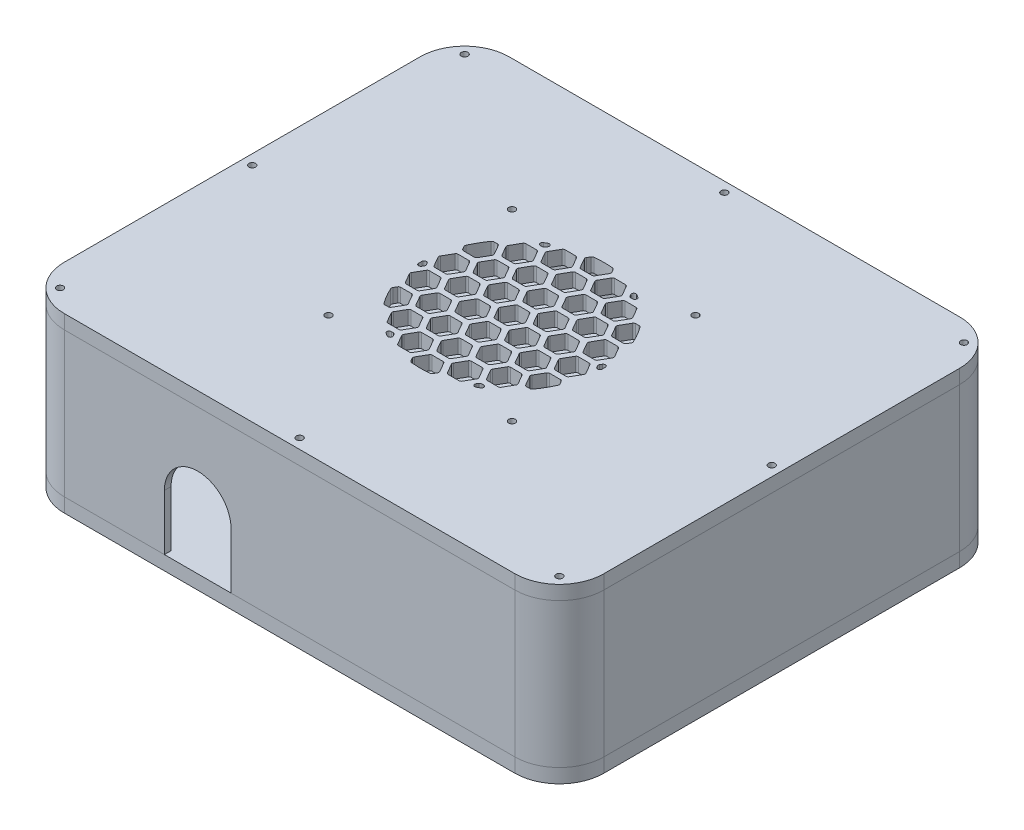
SolidWorks part; units mm, degrees
ref_plane "Front Plane" through (0, 0, 0) normal (0, 0, 1) x (1, 0, 0)
ref_plane "Top Plane" through (0, 0, 0) normal (0, 1, 0) x (1, 0, 0)
ref_plane "Right Plane" through (0, 0, 0) normal (1, 0, 0) x (0, 0, -1)
sketch "Sketch1" plane through (0, 0, 0) normal (0, 1, 0) x (1, 0, 0)
  line L0 (0, 100) -> (242.6, 100) construction
  line L1 (0, 0) -> (242.6, 0)
  line L2 (0, 0) -> (0, 200)
  line L3 (0, 200) -> (242.6, 200)
  line L4 (242.6, 0) -> (242.6, 200)
  line L6 (89, 170) -> (165.6, 170) construction
  line L7 (89, 170) -> (89, 15) construction
  line L8 (89, 15) -> (165.6, 15) construction
  line L9 (165.6, 170) -> (165.6, 15) construction
  line L10 (15, 106) -> (84, 106) construction
  line L11 (15, 106) -> (15, 15) construction
  line L12 (15, 15) -> (84, 15) construction
  line L13 (84, 106) -> (84, 15) construction
  line L14 (170.6, 127) -> (230.6, 127) construction
  line L15 (170.6, 127) -> (170.6, 15) construction
  line L16 (170.6, 15) -> (230.6, 15) construction
  line L17 (230.6, 127) -> (230.6, 15) construction
  line L22 (15, 170) -> (84, 170) construction
  line L23 (15, 170) -> (15, 121) construction
  line L24 (15, 121) -> (84, 121) construction
  line L25 (84, 170) -> (84, 121) construction
  dimension "D1" = 76.6
  dimension "D2" = 155
  dimension "D3" = 69
  dimension "D4" = 91
  dimension "D5" = 60
  dimension "D6" = 112
  dimension "D7" = 15
  dimension "D8" = 5
  dimension "D9" = 5
  dimension "D10" = 12
  dimension "D11" = 30
  dimension "D12" = 15
  dimension "D13" = 15
extrude "Boss-Extrude1" add sketch "Sketch1" along normal blind 6.35
fillet "Fillet1" radius 20 4 edges at (0, 3.175, -200) (242.6, 3.175, -200) (242.6, 3.175, 0) (0, 3.175, 0)
sketch "Sketch2" plane through (0, 6.35, 0) normal (0, 1, 0) x (1, 0, 0)
  line L0 (89, 170) -> (165.6, 170) construction
  line L1 (92.6, 167) -> (162, 167) construction
  line L2 (92.6, 167) -> (92.6, 25) construction
  line L3 (92.6, 25) -> (162, 25) construction
  line L4 (162, 167) -> (162, 25) construction
  line L5 (170.6, 127) -> (230.6, 127) construction
  line L6 (175.6, 65) -> (225.6, 65) construction
  line L7 (175.6, 65) -> (175.6, 40) construction
  line L8 (175.6, 40) -> (225.6, 40) construction
  line L9 (225.6, 65) -> (225.6, 40) construction
  line L11 (15, 170) -> (15, 121) construction
  line L12 (80.996, 125.18) -> (18.004, 125.18) construction
  line L13 (80.996, 125.18) -> (80.996, 165.82) construction
  line L14 (80.996, 165.82) -> (18.004, 165.82) construction
  line L15 (18.004, 125.18) -> (18.004, 165.82) construction
  line L16 (80.996, 125.18) -> (18.004, 165.82) construction
  line L17 (80.996, 165.82) -> (18.004, 125.18) construction
  line L18 (15, 170) -> (84, 170) construction
  line L19 (20, 0) -> (222.6, 0) construction
  circle A0 centre (92.6, 167) radius 1.5
  circle A1 centre (92.6, 25) radius 1.5
  circle A2 centre (162, 25) radius 1.5
  circle A3 centre (162, 167) radius 1.5
  circle A4 centre (175.6, 65) radius 1.5
  circle A5 centre (175.6, 40) radius 1.5
  circle A6 centre (225.6, 65) radius 1.5
  circle A7 centre (225.6, 40) radius 1.5
  circle A8 centre (18.004, 165.82) radius 1.5
  circle A9 centre (80.996, 165.82) radius 1.5
  circle A10 centre (80.996, 125.18) radius 1.5
  circle A11 centre (18.004, 125.18) radius 1.5
  point P6 (127.3, 167)
  point P7 (127.3, 170)
  point P20 (200.6, 65)
  point P23 (200.6, 127)
  point P26 (49.5, 145.5)
  point P34 (15, 145.5)
  point P37 (49.5, 170)
  dimension "D6" = 3
  dimension "D1" = 69.4
  dimension "D2" = 142
  dimension "D3" = 3
  dimension "D4" = 50
  dimension "D5" = 25
  dimension "D7" = 40
  dimension "D8" = 62.992
  dimension "D9" = 40.64
extrude "Cut-Extrude1" cut sketch "Sketch2" against normal through all
sketch "Sketch3" plane through (0, 6.35, 0) normal (0, 1, 0) x (1, 0, 0)
  line L21 (20, 20) -> (9.0398, 9.0398) construction
  line L22 (0, 180) -> (0, 20) construction
  line L23 (6.565, 11.5147) -> (5.7618, 10.7116)
  line L24 (11.5147, 6.565) -> (10.7116, 5.7618)
  line L25 (0, 100) -> (242.6, 100) construction
  line L26 (121.3, 200) -> (121.3, 0) construction
  line L27 (231.0853, 6.565) -> (231.8884, 5.7618)
  line L28 (236.035, 11.5147) -> (236.8382, 10.7116)
  line L29 (236.035, 188.4853) -> (236.8382, 189.2884)
  line L30 (231.0853, 193.435) -> (231.8884, 194.2382)
  line L31 (11.5147, 193.435) -> (10.7116, 194.2382)
  line L32 (6.565, 188.4853) -> (5.7618, 189.2884)
  line L33 (242.6, 20) -> (242.6, 180) construction
  line L34 (20, 0) -> (222.6, 0) construction
  line L35 (222.6, 200) -> (20, 200) construction
  line L36 (20, 20) -> (20, 12.5101) construction
  line L37 (3, 180) -> (3, 20)
  line L38 (20, 3) -> (222.6, 3)
  line L39 (239.6, 20) -> (239.6, 180)
  line L40 (222.6, 197) -> (20, 197)
  line L41 (222.6, 200) -> (20, 200)
  line L42 (0, 180) -> (0, 20)
  line L43 (20, 0) -> (222.6, 0)
  line L44 (242.6, 20) -> (242.6, 180)
  line L45 (222.6, 200) -> (20, 200)
  line L46 (0, 180) -> (0, 20)
  line L47 (20, 0) -> (222.6, 0)
  line L48 (242.6, 20) -> (242.6, 180)
  line L49 (4.5, 103.5) -> (3, 103.5)
  line L50 (3, 103.5) -> (3, 96.5)
  line L51 (3, 96.5) -> (4.5, 96.5)
  line L52 (239.6, 103.5) -> (239.6, 96.5)
  line L53 (238.1, 103.5) -> (239.6, 103.5)
  line L54 (239.6, 96.5) -> (238.1, 96.5)
  line L55 (117.8, 195.5) -> (117.8, 197)
  line L56 (124.8, 195.5) -> (124.8, 197)
  line L57 (117.8, 197) -> (124.8, 197)
  line L58 (117.8, 4.5) -> (117.8, 3)
  line L59 (124.8, 4.5) -> (124.8, 3)
  line L60 (117.8, 3) -> (124.8, 3)
  arc A22 (10.7116, 194.2382) -> (5.7618, 189.2884) centre (20, 180) ccw
  arc A24 (5.7618, 10.7116) -> (10.7116, 5.7618) centre (20, 20) ccw
  arc A26 (231.8884, 5.7618) -> (236.8382, 10.7116) centre (222.6, 20) ccw
  arc A28 (236.8382, 189.2884) -> (231.8884, 194.2382) centre (222.6, 180) ccw
  arc A43 (11.5147, 6.565) -> (6.565, 11.5147) centre (9.0398, 9.0398) ccw
  circle A44 centre (9.0398, 9.0398) radius 1.5
  circle A45 centre (233.5602, 9.0398) radius 1.5
  arc A46 (231.0853, 6.565) -> (236.035, 11.5147) centre (233.5602, 9.0398) cw
  circle A47 centre (233.5602, 190.9602) radius 1.5
  arc A48 (231.0853, 193.435) -> (236.035, 188.4853) centre (233.5602, 190.9602) ccw
  circle A49 centre (9.0398, 190.9602) radius 1.5
  arc A50 (11.5147, 193.435) -> (6.565, 188.4853) centre (9.0398, 190.9602) cw
  arc A51 (222.6, 0) -> (242.6, 20) centre (222.6, 20) ccw construction
  arc A52 (0, 20) -> (20, 0) centre (20, 20) ccw construction
  arc A53 (242.6, 180) -> (222.6, 200) centre (222.6, 180) ccw construction
  arc A54 (20, 200) -> (0, 180) centre (20, 180) ccw construction
  arc A55 (3, 20) -> (20, 3) centre (20, 20) ccw
  arc A56 (222.6, 3) -> (239.6, 20) centre (222.6, 20) ccw
  arc A57 (239.6, 180) -> (222.6, 197) centre (222.6, 180) ccw
  arc A58 (20, 197) -> (3, 180) centre (20, 180) ccw
  arc A59 (20, 200) -> (0, 180) centre (20, 180) ccw
  arc A60 (0, 20) -> (20, 0) centre (20, 20) ccw
  arc A61 (222.6, 0) -> (242.6, 20) centre (222.6, 20) ccw
  arc A62 (242.6, 180) -> (222.6, 200) centre (222.6, 180) ccw
  arc A63 (20, 200) -> (0, 180) centre (20, 180) ccw
  arc A64 (0, 20) -> (20, 0) centre (20, 20) ccw
  arc A65 (222.6, 0) -> (242.6, 20) centre (222.6, 20) ccw
  arc A66 (242.6, 180) -> (222.6, 200) centre (222.6, 180) ccw
  arc A67 (4.5, 96.5) -> (4.5, 103.5) centre (4.5, 100) ccw
  circle A68 centre (4.5, 100) radius 1.5
  arc A69 (238.1, 96.5) -> (238.1, 103.5) centre (238.1, 100) cw
  circle A70 centre (238.1, 100) radius 1.5
  circle A71 centre (121.3, 195.5) radius 1.5
  arc A72 (117.8, 195.5) -> (124.8, 195.5) centre (121.3, 195.5) ccw
  circle A73 centre (121.3, 4.5) radius 1.5
  arc A74 (117.8, 4.5) -> (124.8, 4.5) centre (121.3, 4.5) cw
  line M50 (222.6, 200) -> (20, 200)
  arc M51 (20, 200) -> (0, 180) centre (20, 180) ccw
  line M52 (0, 180) -> (0, 20)
  arc M53 (0, 20) -> (20, 0) centre (20, 20) ccw
  line M54 (20, 0) -> (222.6, 0)
  arc M55 (222.6, 0) -> (242.6, 20) centre (222.6, 20) ccw
  line M56 (242.6, 20) -> (242.6, 180)
  arc M57 (242.6, 180) -> (222.6, 200) centre (222.6, 180) ccw
  dimension "D3" = 0
  dimension "D4" = 7
  dimension "D5" = 3
  dimension "D1" = 3
  dimension "D7" = 3
  dimension "D6" = 3
  dimension "D2" = 45
extrude "Boss-Extrude2" add sketch "Sketch3" along normal blind 65 separate body contours M57 M50 M51 M52 M53 M54 M55 M56 | A50 L31 A22 A49 L32 | L37 A68 L50 L51 A67 L49 | A24 A44 L24 A43 L23 | A46 L27 A26 A45 L28 | A74 L58 L38 A73 L60 L59 | L39 A70 L52 L53 A69 L54 | L30 A48 L29 A28 A47 | L55 A72 L56 L40 A71 L57 region at (11.4469, 6.35, -11.4469) region at (3.086, 6.35, -98.25) region at (117.886, 6.35, -3.75) region at (6.8741, 6.35, -190.6517) region at (231.5546, 6.35, -6.2312) region at (119.55, 6.35, -196.914) region at (238.85, 6.35, -96.586) region at (233.2517, 6.35, -193.1259) region at (236.5198, 6.35, -193.9198)
fillet "Fillet5" radius 2 16 edges at (10.7116, 38.85, -194.2382) (5.7618, 38.85, -189.2884) (3, 38.85, -103.5) (3, 38.85, -96.5) (5.7618, 38.85, -10.7116) (10.7116, 38.85, -5.7618) (117.8, 38.85, -3) (124.8, 38.85, -3) (231.8884, 38.85, -5.7618) (236.8382, 38.85, -10.7116) (239.6, 38.85, -96.5) (239.6, 38.85, -103.5) (231.8884, 38.85, -194.2382) (124.8, 38.85, -197) (117.8, 38.85, -197) (236.8382, 38.85, -189.2884)
sketch "Sketch4" plane through (0, 71.35, 0) normal (0, 1, 0) x (1, 0, 0)
  line L4 (0, 180) -> (0, 20)
  line L5 (222.6, 200) -> (20, 200)
  line L6 (242.6, 20) -> (242.6, 180)
  line L7 (20, 0) -> (222.6, 0)
  line L8 (0, 180) -> (0, 20)
  line L9 (222.6, 200) -> (20, 200)
  line L10 (242.6, 20) -> (242.6, 180)
  line L11 (20, 0) -> (222.6, 0)
  arc A4 (20, 200) -> (0, 180) centre (20, 180) ccw
  arc A5 (242.6, 180) -> (222.6, 200) centre (222.6, 180) ccw
  arc A6 (222.6, 0) -> (242.6, 20) centre (222.6, 20) ccw
  arc A7 (0, 20) -> (20, 0) centre (20, 20) ccw
  arc A8 (20, 200) -> (0, 180) centre (20, 180) ccw
  arc A9 (242.6, 180) -> (222.6, 200) centre (222.6, 180) ccw
  arc A10 (222.6, 0) -> (242.6, 20) centre (222.6, 20) ccw
  arc A11 (0, 20) -> (20, 0) centre (20, 20) ccw
  dimension "D1" = 0
extrude "Boss-Extrude4" add sketch "Sketch4" along normal blind 6.35 separate body
sketch "Sketch5" plane through (0, 77.7, 0) normal (0, 1, 0) x (1, 0, 0)
  line L1 (80.05, 141.25) -> (162.55, 141.25) construction
  line L2 (80.05, 141.25) -> (80.05, 58.75) construction
  line L3 (80.05, 58.75) -> (162.55, 58.75) construction
  line L4 (162.55, 141.25) -> (162.55, 58.75) construction
  line L5 (80.05, 141.25) -> (162.55, 58.75) construction
  line L6 (80.05, 58.75) -> (162.55, 141.25) construction
  line L8 (222.6, 200) -> (20, 200) construction
  line L9 (0, 180) -> (0, 20) construction
  circle A0 centre (80.05, 141.25) radius 1.5
  circle A1 centre (80.05, 58.75) radius 1.5
  circle A2 centre (162.55, 58.75) radius 1.5
  circle A3 centre (162.55, 141.25) radius 1.5
  point P0 (121.3, 100)
  point P11 (121.3, 200)
  point P12 (0, 100)
  dimension "D2" = 3
  dimension "D1" = 82.5
extrude "Cut-Extrude2" cut sketch "Sketch5" against normal through all
sketch "Sketch6" plane through (0, 77.7, 0) normal (0, 1, 0) x (1, 0, 0)
  circle A20 centre (121.3, 4.5) radius 1.5 construction
  circle A21 centre (233.5602, 9.0398) radius 1.5 construction
  circle A22 centre (238.1, 100) radius 1.5 construction
  circle A23 centre (233.5602, 190.9602) radius 1.5 construction
  circle A24 centre (121.3, 195.5) radius 1.5 construction
  circle A25 centre (9.0398, 190.9602) radius 1.5 construction
  circle A26 centre (4.5, 100) radius 1.5 construction
  circle A27 centre (9.0398, 9.0398) radius 1.5 construction
  circle A28 centre (121.3, 4.5) radius 1.5
  circle A29 centre (233.5602, 9.0398) radius 1.5
  circle A30 centre (238.1, 100) radius 1.5
  circle A31 centre (233.5602, 190.9602) radius 1.5
  circle A32 centre (121.3, 195.5) radius 1.5
  circle A33 centre (9.0398, 190.9602) radius 1.5
  circle A34 centre (4.5, 100) radius 1.5
  circle A35 centre (9.0398, 9.0398) radius 1.5
extrude "Cut-Extrude3" cut sketch "Sketch6" against normal through all
sketch "Sketch7" plane through (0, 77.7, 0) normal (0, 1, 0) x (1, 0, 0)
  line L0 (80.05, 141.25) -> (162.55, 141.25) construction
  line L1 (80.05, 141.25) -> (80.05, 58.75) construction
  line L2 (80.05, 58.75) -> (162.55, 58.75) construction
  line L3 (162.55, 141.25) -> (162.55, 58.75) construction
  line L4 (80.05, 141.25) -> (162.55, 141.25) construction
  line L5 (80.05, 141.25) -> (80.05, 58.75) construction
  line L6 (80.05, 58.75) -> (162.55, 58.75) construction
  line L7 (162.55, 141.25) -> (162.55, 58.75) construction
  line L8 (157.7952, 124.5346) -> (151.7952, 124.5346)
  line L9 (124.3, 105.1962) -> (118.3, 105.1962)
  line L10 (118.3, 105.1962) -> (115.3, 100)
  line L11 (115.3, 100) -> (118.3, 94.8038)
  line L12 (118.3, 94.8038) -> (124.3, 94.8038)
  line L13 (124.3, 94.8038) -> (127.3, 100)
  line L14 (127.3, 100) -> (124.3, 105.1962)
  line L15 (138.4651, 106.4462) -> (135.4651, 111.6423)
  line L16 (135.4651, 111.6423) -> (129.4651, 111.6423)
  line L17 (129.4651, 111.6423) -> (126.4651, 106.4462)
  line L18 (126.4651, 106.4462) -> (129.4651, 101.25)
  line L19 (129.4651, 101.25) -> (135.4651, 101.25)
  line L20 (135.4651, 101.25) -> (138.4651, 106.4462)
  line L21 (127.3, 112.8923) -> (124.3, 118.0885)
  line L22 (124.3, 118.0885) -> (118.3, 118.0885)
  line L23 (118.3, 118.0885) -> (115.3, 112.8923)
  line L24 (115.3, 112.8923) -> (118.3, 107.6962)
  line L25 (118.3, 107.6962) -> (124.3, 107.6962)
  line L26 (124.3, 107.6962) -> (127.3, 112.8923)
  line L27 (135.4651, 124.5346) -> (129.4651, 124.5346)
  line L28 (129.4651, 124.5346) -> (126.4651, 119.3385)
  line L29 (126.4651, 119.3385) -> (129.4651, 114.1423)
  line L30 (129.4651, 114.1423) -> (135.4651, 114.1423)
  line L31 (135.4651, 114.1423) -> (138.4651, 119.3385)
  line L32 (138.4651, 119.3385) -> (135.4651, 124.5346)
  line L33 (151.7952, 124.5346) -> (148.7952, 119.3385)
  line L34 (148.7952, 119.3385) -> (151.7952, 114.1423)
  line L35 (151.7952, 114.1423) -> (157.7952, 114.1423)
  line L36 (157.7952, 114.1423) -> (160.7952, 119.3385)
  line L37 (160.7952, 119.3385) -> (157.7952, 124.5346)
  line L38 (149.6301, 112.8923) -> (146.6301, 118.0885)
  line L39 (146.6301, 118.0885) -> (140.6301, 118.0885)
  line L40 (140.6301, 118.0885) -> (137.6301, 112.8923)
  line L41 (137.6301, 112.8923) -> (140.6301, 107.6962)
  line L42 (140.6301, 107.6962) -> (146.6301, 107.6962)
  line L43 (146.6301, 107.6962) -> (149.6301, 112.8923)
  line L44 (146.6301, 105.1962) -> (140.6301, 105.1962)
  line L45 (140.6301, 105.1962) -> (137.6301, 100)
  line L46 (137.6301, 100) -> (140.6301, 94.8038)
  line L47 (140.6301, 94.8038) -> (146.6301, 94.8038)
  line L48 (146.6301, 94.8038) -> (149.6301, 100)
  line L49 (149.6301, 100) -> (146.6301, 105.1962)
  line L50 (160.7952, 106.4462) -> (157.7952, 111.6423)
  line L51 (157.7952, 111.6423) -> (151.7952, 111.6423)
  line L52 (151.7952, 111.6423) -> (148.7952, 106.4462)
  line L53 (148.7952, 106.4462) -> (151.7952, 101.25)
  line L54 (151.7952, 101.25) -> (157.7952, 101.25)
  line L55 (157.7952, 101.25) -> (160.7952, 106.4462)
  line L56 (180.1253, 124.5346) -> (174.1253, 124.5346)
  line L57 (174.1253, 124.5346) -> (171.1253, 119.3385)
  line L58 (171.1253, 119.3385) -> (174.1253, 114.1423)
  line L59 (174.1253, 114.1423) -> (180.1253, 114.1423)
  line L60 (180.1253, 114.1423) -> (183.1253, 119.3385)
  line L61 (183.1253, 119.3385) -> (180.1253, 124.5346)
  line L62 (171.9603, 112.8923) -> (168.9603, 118.0885)
  line L63 (168.9603, 118.0885) -> (162.9603, 118.0885)
  line L64 (162.9603, 118.0885) -> (159.9603, 112.8923)
  line L65 (159.9603, 112.8923) -> (162.9603, 107.6962)
  line L66 (162.9603, 107.6962) -> (168.9603, 107.6962)
  line L67 (168.9603, 107.6962) -> (171.9603, 112.8923)
  line L68 (168.9603, 105.1962) -> (162.9603, 105.1962)
  line L69 (162.9603, 105.1962) -> (159.9603, 100)
  line L70 (159.9603, 100) -> (162.9603, 94.8038)
  line L71 (162.9603, 94.8038) -> (168.9603, 94.8038)
  line L72 (168.9603, 94.8038) -> (171.9603, 100)
  line L73 (171.9603, 100) -> (168.9603, 105.1962)
  line L74 (183.1253, 106.4462) -> (180.1253, 111.6423)
  line L75 (180.1253, 111.6423) -> (174.1253, 111.6423)
  line L76 (174.1253, 111.6423) -> (171.1253, 106.4462)
  line L77 (171.1253, 106.4462) -> (174.1253, 101.25)
  line L78 (174.1253, 101.25) -> (180.1253, 101.25)
  line L79 (180.1253, 101.25) -> (183.1253, 106.4462)
  line L80 (157.7952, 150.3192) -> (151.7952, 150.3192)
  line L81 (151.7952, 150.3192) -> (148.7952, 145.1231)
  line L82 (148.7952, 145.1231) -> (151.7952, 139.9269)
  line L83 (151.7952, 139.9269) -> (157.7952, 139.9269)
  line L84 (157.7952, 139.9269) -> (160.7952, 145.1231)
  line L85 (160.7952, 145.1231) -> (157.7952, 150.3192)
  line L86 (149.6301, 138.6769) -> (146.6301, 143.8731)
  line L87 (146.6301, 143.8731) -> (140.6301, 143.8731)
  line L88 (140.6301, 143.8731) -> (137.6301, 138.6769)
  line L89 (137.6301, 138.6769) -> (140.6301, 133.4808)
  line L90 (140.6301, 133.4808) -> (146.6301, 133.4808)
  line L91 (146.6301, 133.4808) -> (149.6301, 138.6769)
  line L92 (146.6301, 130.9808) -> (140.6301, 130.9808)
  line L93 (140.6301, 130.9808) -> (137.6301, 125.7846)
  line L94 (137.6301, 125.7846) -> (140.6301, 120.5885)
  line L95 (140.6301, 120.5885) -> (146.6301, 120.5885)
  line L96 (146.6301, 120.5885) -> (149.6301, 125.7846)
  line L97 (149.6301, 125.7846) -> (146.6301, 130.9808)
  line L98 (160.7952, 132.2308) -> (157.7952, 137.4269)
  line L99 (157.7952, 137.4269) -> (151.7952, 137.4269)
  line L100 (151.7952, 137.4269) -> (148.7952, 132.2308)
  line L101 (148.7952, 132.2308) -> (151.7952, 127.0346)
  line L102 (151.7952, 127.0346) -> (157.7952, 127.0346)
  line L103 (157.7952, 127.0346) -> (160.7952, 132.2308)
  line L104 (180.1253, 150.3192) -> (174.1253, 150.3192)
  line L105 (174.1253, 150.3192) -> (171.1253, 145.1231)
  line L106 (171.1253, 145.1231) -> (174.1253, 139.9269)
  line L107 (174.1253, 139.9269) -> (180.1253, 139.9269)
  line L108 (180.1253, 139.9269) -> (183.1253, 145.1231)
  line L109 (183.1253, 145.1231) -> (180.1253, 150.3192)
  line L110 (171.9603, 138.6769) -> (168.9603, 143.8731)
  line L111 (168.9603, 143.8731) -> (162.9603, 143.8731)
  line L112 (162.9603, 143.8731) -> (159.9603, 138.6769)
  line L113 (159.9603, 138.6769) -> (162.9603, 133.4808)
  line L114 (162.9603, 133.4808) -> (168.9603, 133.4808)
  line L115 (168.9603, 133.4808) -> (171.9603, 138.6769)
  line L116 (168.9603, 130.9808) -> (162.9603, 130.9808)
  line L117 (162.9603, 130.9808) -> (159.9603, 125.7846)
  line L118 (159.9603, 125.7846) -> (162.9603, 120.5885)
  line L119 (162.9603, 120.5885) -> (168.9603, 120.5885)
  line L120 (168.9603, 120.5885) -> (171.9603, 125.7846)
  line L121 (171.9603, 125.7846) -> (168.9603, 130.9808)
  line L122 (183.1253, 132.2308) -> (180.1253, 137.4269)
  line L123 (180.1253, 137.4269) -> (174.1253, 137.4269)
  line L124 (174.1253, 137.4269) -> (171.1253, 132.2308)
  line L125 (171.1253, 132.2308) -> (174.1253, 127.0346)
  line L126 (174.1253, 127.0346) -> (180.1253, 127.0346)
  line L127 (180.1253, 127.0346) -> (183.1253, 132.2308)
  line L128 (135.4651, 150.3192) -> (129.4651, 150.3192)
  line L129 (129.4651, 150.3192) -> (126.4651, 145.1231)
  line L130 (126.4651, 145.1231) -> (129.4651, 139.9269)
  line L131 (129.4651, 139.9269) -> (135.4651, 139.9269)
  line L132 (135.4651, 139.9269) -> (138.4651, 145.1231)
  line L133 (138.4651, 145.1231) -> (135.4651, 150.3192)
  line L134 (127.3, 138.6769) -> (124.3, 143.8731)
  line L135 (124.3, 143.8731) -> (118.3, 143.8731)
  line L136 (118.3, 143.8731) -> (115.3, 138.6769)
  line L137 (115.3, 138.6769) -> (118.3, 133.4808)
  line L138 (118.3, 133.4808) -> (124.3, 133.4808)
  line L139 (124.3, 133.4808) -> (127.3, 138.6769)
  line L140 (124.3, 130.9808) -> (118.3, 130.9808)
  line L141 (118.3, 130.9808) -> (115.3, 125.7846)
  line L142 (115.3, 125.7846) -> (118.3, 120.5885)
  line L143 (118.3, 120.5885) -> (124.3, 120.5885)
  line L144 (124.3, 120.5885) -> (127.3, 125.7846)
  line L145 (127.3, 125.7846) -> (124.3, 130.9808)
  line L146 (138.4651, 132.2308) -> (135.4651, 137.4269)
  line L147 (135.4651, 137.4269) -> (129.4651, 137.4269)
  line L148 (129.4651, 137.4269) -> (126.4651, 132.2308)
  line L149 (126.4651, 132.2308) -> (129.4651, 127.0346)
  line L150 (129.4651, 127.0346) -> (135.4651, 127.0346)
  line L151 (135.4651, 127.0346) -> (138.4651, 132.2308)
  line L152 (124.3, 92.3038) -> (118.3, 92.3038)
  line L153 (118.3, 92.3038) -> (115.3, 87.1077)
  line L154 (115.3, 87.1077) -> (118.3, 81.9115)
  line L155 (118.3, 81.9115) -> (124.3, 81.9115)
  line L156 (124.3, 81.9115) -> (127.3, 87.1077)
  line L157 (127.3, 87.1077) -> (124.3, 92.3038)
  line L158 (138.4651, 93.5538) -> (135.4651, 98.75)
  line L159 (135.4651, 98.75) -> (129.4651, 98.75)
  line L160 (129.4651, 98.75) -> (126.4651, 93.5538)
  line L161 (126.4651, 93.5538) -> (129.4651, 88.3577)
  line L162 (129.4651, 88.3577) -> (135.4651, 88.3577)
  line L163 (135.4651, 88.3577) -> (138.4651, 93.5538)
  line L164 (160.7952, 93.5538) -> (157.7952, 98.75)
  line L165 (157.7952, 98.75) -> (151.7952, 98.75)
  line L166 (151.7952, 98.75) -> (148.7952, 93.5538)
  line L167 (148.7952, 93.5538) -> (151.7952, 88.3577)
  line L168 (151.7952, 88.3577) -> (157.7952, 88.3577)
  line L169 (157.7952, 88.3577) -> (160.7952, 93.5538)
  line L170 (168.9603, 92.3038) -> (162.9603, 92.3038)
  line L171 (162.9603, 92.3038) -> (159.9603, 87.1077)
  line L172 (159.9603, 87.1077) -> (162.9603, 81.9115)
  line L173 (162.9603, 81.9115) -> (168.9603, 81.9115)
  line L174 (168.9603, 81.9115) -> (171.9603, 87.1077)
  line L175 (171.9603, 87.1077) -> (168.9603, 92.3038)
  line L176 (146.6301, 92.3038) -> (140.6301, 92.3038)
  line L177 (140.6301, 92.3038) -> (137.6301, 87.1077)
  line L178 (137.6301, 87.1077) -> (140.6301, 81.9115)
  line L179 (140.6301, 81.9115) -> (146.6301, 81.9115)
  line L180 (146.6301, 81.9115) -> (149.6301, 87.1077)
  line L181 (149.6301, 87.1077) -> (146.6301, 92.3038)
  line L182 (124.3, 79.4115) -> (118.3, 79.4115)
  line L183 (118.3, 79.4115) -> (115.3, 74.2154)
  line L184 (115.3, 74.2154) -> (118.3, 69.0192)
  line L185 (118.3, 69.0192) -> (124.3, 69.0192)
  line L186 (124.3, 69.0192) -> (127.3, 74.2154)
  line L187 (127.3, 74.2154) -> (124.3, 79.4115)
  line L188 (138.4651, 80.6615) -> (135.4651, 85.8577)
  line L189 (135.4651, 85.8577) -> (129.4651, 85.8577)
  line L190 (129.4651, 85.8577) -> (126.4651, 80.6615)
  line L191 (126.4651, 80.6615) -> (129.4651, 75.4654)
  line L192 (129.4651, 75.4654) -> (135.4651, 75.4654)
  line L193 (135.4651, 75.4654) -> (138.4651, 80.6615)
  line L194 (160.7952, 80.6615) -> (157.7952, 85.8577)
  line L195 (157.7952, 85.8577) -> (151.7952, 85.8577)
  line L196 (151.7952, 85.8577) -> (148.7952, 80.6615)
  line L197 (148.7952, 80.6615) -> (151.7952, 75.4654)
  line L198 (151.7952, 75.4654) -> (157.7952, 75.4654)
  line L199 (157.7952, 75.4654) -> (160.7952, 80.6615)
  line L200 (168.9603, 79.4115) -> (162.9603, 79.4115)
  line L201 (162.9603, 79.4115) -> (159.9603, 74.2154)
  line L202 (159.9603, 74.2154) -> (162.9603, 69.0192)
  line L203 (162.9603, 69.0192) -> (168.9603, 69.0192)
  line L204 (168.9603, 69.0192) -> (171.9603, 74.2154)
  line L205 (171.9603, 74.2154) -> (168.9603, 79.4115)
  line L206 (146.6301, 79.4115) -> (140.6301, 79.4115)
  line L207 (140.6301, 79.4115) -> (137.6301, 74.2154)
  line L208 (137.6301, 74.2154) -> (140.6301, 69.0192)
  line L209 (140.6301, 69.0192) -> (146.6301, 69.0192)
  line L210 (146.6301, 69.0192) -> (149.6301, 74.2154)
  line L211 (149.6301, 74.2154) -> (146.6301, 79.4115)
  line L212 (124.3, 66.5192) -> (118.3, 66.5192)
  line L213 (118.3, 66.5192) -> (115.3, 61.3231)
  line L214 (115.3, 61.3231) -> (118.3, 56.1269)
  line L215 (118.3, 56.1269) -> (124.3, 56.1269)
  line L216 (124.3, 56.1269) -> (127.3, 61.3231)
  line L217 (127.3, 61.3231) -> (124.3, 66.5192)
  line L218 (138.4651, 67.7692) -> (135.4651, 72.9654)
  line L219 (135.4651, 72.9654) -> (129.4651, 72.9654)
  line L220 (129.4651, 72.9654) -> (126.4651, 67.7692)
  line L221 (126.4651, 67.7692) -> (129.4651, 62.5731)
  line L222 (129.4651, 62.5731) -> (135.4651, 62.5731)
  line L223 (135.4651, 62.5731) -> (138.4651, 67.7692)
  line L224 (160.7952, 67.7692) -> (157.7952, 72.9654)
  line L225 (157.7952, 72.9654) -> (151.7952, 72.9654)
  line L226 (151.7952, 72.9654) -> (148.7952, 67.7692)
  line L227 (148.7952, 67.7692) -> (151.7952, 62.5731)
  line L228 (151.7952, 62.5731) -> (157.7952, 62.5731)
  line L229 (157.7952, 62.5731) -> (160.7952, 67.7692)
  line L230 (168.9603, 66.5192) -> (162.9603, 66.5192)
  line L231 (162.9603, 66.5192) -> (159.9603, 61.3231)
  line L232 (159.9603, 61.3231) -> (162.9603, 56.1269)
  line L233 (162.9603, 56.1269) -> (168.9603, 56.1269)
  line L234 (168.9603, 56.1269) -> (171.9603, 61.3231)
  line L235 (171.9603, 61.3231) -> (168.9603, 66.5192)
  line L236 (146.6301, 66.5192) -> (140.6301, 66.5192)
  line L237 (140.6301, 66.5192) -> (137.6301, 61.3231)
  line L238 (137.6301, 61.3231) -> (140.6301, 56.1269)
  line L239 (140.6301, 56.1269) -> (146.6301, 56.1269)
  line L240 (146.6301, 56.1269) -> (149.6301, 61.3231)
  line L241 (149.6301, 61.3231) -> (146.6301, 66.5192)
  line L242 (124.3, 53.6269) -> (118.3, 53.6269)
  line L243 (118.3, 53.6269) -> (115.3, 48.4308)
  line L244 (115.3, 48.4308) -> (118.3, 43.2346)
  line L245 (118.3, 43.2346) -> (124.3, 43.2346)
  line L246 (124.3, 43.2346) -> (127.3, 48.4308)
  line L247 (127.3, 48.4308) -> (124.3, 53.6269)
  line L248 (138.4651, 54.8769) -> (135.4651, 60.0731)
  line L249 (135.4651, 60.0731) -> (129.4651, 60.0731)
  line L250 (129.4651, 60.0731) -> (126.4651, 54.8769)
  line L251 (126.4651, 54.8769) -> (129.4651, 49.6808)
  line L252 (129.4651, 49.6808) -> (135.4651, 49.6808)
  line L253 (135.4651, 49.6808) -> (138.4651, 54.8769)
  line L254 (160.7952, 54.8769) -> (157.7952, 60.0731)
  line L255 (157.7952, 60.0731) -> (151.7952, 60.0731)
  line L256 (151.7952, 60.0731) -> (148.7952, 54.8769)
  line L257 (148.7952, 54.8769) -> (151.7952, 49.6808)
  line L258 (151.7952, 49.6808) -> (157.7952, 49.6808)
  line L259 (157.7952, 49.6808) -> (160.7952, 54.8769)
  line L260 (168.9603, 53.6269) -> (162.9603, 53.6269)
  line L261 (162.9603, 53.6269) -> (159.9603, 48.4308)
  line L262 (159.9603, 48.4308) -> (162.9603, 43.2346)
  line L263 (162.9603, 43.2346) -> (168.9603, 43.2346)
  line L264 (168.9603, 43.2346) -> (171.9603, 48.4308)
  line L265 (171.9603, 48.4308) -> (168.9603, 53.6269)
  line L266 (146.6301, 53.6269) -> (140.6301, 53.6269)
  line L267 (140.6301, 53.6269) -> (137.6301, 48.4308)
  line L268 (137.6301, 48.4308) -> (140.6301, 43.2346)
  line L269 (140.6301, 43.2346) -> (146.6301, 43.2346)
  line L270 (146.6301, 43.2346) -> (149.6301, 48.4308)
  line L271 (149.6301, 48.4308) -> (146.6301, 53.6269)
  line L272 (104.9699, 138.6769) -> (101.9699, 143.8731)
  line L273 (101.9699, 143.8731) -> (95.9699, 143.8731)
  line L274 (95.9699, 143.8731) -> (92.9699, 138.6769)
  line L275 (92.9699, 138.6769) -> (95.9699, 133.4808)
  line L276 (95.9699, 133.4808) -> (101.9699, 133.4808)
  line L277 (101.9699, 133.4808) -> (104.9699, 138.6769)
  line L278 (101.9699, 130.9808) -> (95.9699, 130.9808)
  line L279 (95.9699, 130.9808) -> (92.9699, 125.7846)
  line L280 (92.9699, 125.7846) -> (95.9699, 120.5885)
  line L281 (95.9699, 120.5885) -> (101.9699, 120.5885)
  line L282 (101.9699, 120.5885) -> (104.9699, 125.7846)
  line L283 (104.9699, 125.7846) -> (101.9699, 130.9808)
  line L284 (101.9699, 92.3038) -> (95.9699, 92.3038)
  line L285 (95.9699, 92.3038) -> (92.9699, 87.1077)
  line L286 (92.9699, 87.1077) -> (95.9699, 81.9115)
  line L287 (95.9699, 81.9115) -> (101.9699, 81.9115)
  line L288 (101.9699, 81.9115) -> (104.9699, 87.1077)
  line L289 (104.9699, 87.1077) -> (101.9699, 92.3038)
  line L290 (101.9699, 79.4115) -> (95.9699, 79.4115)
  line L291 (95.9699, 79.4115) -> (92.9699, 74.2154)
  line L292 (92.9699, 74.2154) -> (95.9699, 69.0192)
  line L293 (95.9699, 69.0192) -> (101.9699, 69.0192)
  line L294 (101.9699, 69.0192) -> (104.9699, 74.2154)
  line L295 (104.9699, 74.2154) -> (101.9699, 79.4115)
  line L296 (101.9699, 66.5192) -> (95.9699, 66.5192)
  line L297 (95.9699, 66.5192) -> (92.9699, 61.3231)
  line L298 (92.9699, 61.3231) -> (95.9699, 56.1269)
  line L299 (95.9699, 56.1269) -> (101.9699, 56.1269)
  line L300 (101.9699, 56.1269) -> (104.9699, 61.3231)
  line L301 (104.9699, 61.3231) -> (101.9699, 66.5192)
  line L302 (116.1349, 67.7692) -> (113.1349, 72.9654)
  line L303 (113.1349, 72.9654) -> (107.1349, 72.9654)
  line L304 (107.1349, 72.9654) -> (104.1349, 67.7692)
  line L305 (104.1349, 67.7692) -> (107.1349, 62.5731)
  line L306 (107.1349, 62.5731) -> (113.1349, 62.5731)
  line L307 (113.1349, 62.5731) -> (116.1349, 67.7692)
  line L308 (116.1349, 80.6615) -> (113.1349, 85.8577)
  line L309 (113.1349, 85.8577) -> (107.1349, 85.8577)
  line L310 (107.1349, 85.8577) -> (104.1349, 80.6615)
  line L311 (104.1349, 80.6615) -> (107.1349, 75.4654)
  line L312 (107.1349, 75.4654) -> (113.1349, 75.4654)
  line L313 (113.1349, 75.4654) -> (116.1349, 80.6615)
  line L314 (101.9699, 105.1962) -> (95.9699, 105.1962)
  line L315 (95.9699, 105.1962) -> (92.9699, 100)
  line L316 (92.9699, 100) -> (95.9699, 94.8038)
  line L317 (95.9699, 94.8038) -> (101.9699, 94.8038)
  line L318 (101.9699, 94.8038) -> (104.9699, 100)
  line L319 (104.9699, 100) -> (101.9699, 105.1962)
  line L320 (116.1349, 93.5538) -> (113.1349, 98.75)
  line L321 (113.1349, 98.75) -> (107.1349, 98.75)
  line L322 (107.1349, 98.75) -> (104.1349, 93.5538)
  line L323 (104.1349, 93.5538) -> (107.1349, 88.3577)
  line L324 (107.1349, 88.3577) -> (113.1349, 88.3577)
  line L325 (113.1349, 88.3577) -> (116.1349, 93.5538)
  line L326 (116.1349, 106.4462) -> (113.1349, 111.6423)
  line L327 (113.1349, 111.6423) -> (107.1349, 111.6423)
  line L328 (107.1349, 111.6423) -> (104.1349, 106.4462)
  line L329 (104.1349, 106.4462) -> (107.1349, 101.25)
  line L330 (107.1349, 101.25) -> (113.1349, 101.25)
  line L331 (113.1349, 101.25) -> (116.1349, 106.4462)
  line L332 (104.9699, 112.8923) -> (101.9699, 118.0885)
  line L333 (101.9699, 118.0885) -> (95.9699, 118.0885)
  line L334 (95.9699, 118.0885) -> (92.9699, 112.8923)
  line L335 (92.9699, 112.8923) -> (95.9699, 107.6962)
  line L336 (95.9699, 107.6962) -> (101.9699, 107.6962)
  line L337 (101.9699, 107.6962) -> (104.9699, 112.8923)
  line L338 (113.1349, 124.5346) -> (107.1349, 124.5346)
  line L339 (107.1349, 124.5346) -> (104.1349, 119.3385)
  line L340 (104.1349, 119.3385) -> (107.1349, 114.1423)
  line L341 (107.1349, 114.1423) -> (113.1349, 114.1423)
  line L342 (113.1349, 114.1423) -> (116.1349, 119.3385)
  line L343 (116.1349, 119.3385) -> (113.1349, 124.5346)
  line L344 (116.1349, 132.2308) -> (113.1349, 137.4269)
  line L345 (113.1349, 137.4269) -> (107.1349, 137.4269)
  line L346 (107.1349, 137.4269) -> (104.1349, 132.2308)
  line L347 (104.1349, 132.2308) -> (107.1349, 127.0346)
  line L348 (107.1349, 127.0346) -> (113.1349, 127.0346)
  line L349 (113.1349, 127.0346) -> (116.1349, 132.2308)
  line L350 (116.1349, 54.8769) -> (113.1349, 60.0731)
  line L351 (113.1349, 60.0731) -> (107.1349, 60.0731)
  line L352 (107.1349, 60.0731) -> (104.1349, 54.8769)
  line L353 (104.1349, 54.8769) -> (107.1349, 49.6808)
  line L354 (107.1349, 49.6808) -> (113.1349, 49.6808)
  line L355 (113.1349, 49.6808) -> (116.1349, 54.8769)
  line L356 (82.6397, 138.6769) -> (79.6397, 143.8731)
  line L357 (79.6397, 143.8731) -> (73.6397, 143.8731)
  line L358 (73.6397, 143.8731) -> (70.6397, 138.6769)
  line L359 (70.6397, 138.6769) -> (73.6397, 133.4808)
  line L360 (73.6397, 133.4808) -> (79.6397, 133.4808)
  line L361 (79.6397, 133.4808) -> (82.6397, 138.6769)
  line L362 (79.6397, 130.9808) -> (73.6397, 130.9808)
  line L363 (73.6397, 130.9808) -> (70.6397, 125.7846)
  line L364 (70.6397, 125.7846) -> (73.6397, 120.5885)
  line L365 (73.6397, 120.5885) -> (79.6397, 120.5885)
  line L366 (79.6397, 120.5885) -> (82.6397, 125.7846)
  line L367 (82.6397, 125.7846) -> (79.6397, 130.9808)
  line L368 (79.6397, 92.3038) -> (73.6397, 92.3038)
  line L369 (73.6397, 92.3038) -> (70.6397, 87.1077)
  line L370 (70.6397, 87.1077) -> (73.6397, 81.9115)
  line L371 (73.6397, 81.9115) -> (79.6397, 81.9115)
  line L372 (79.6397, 81.9115) -> (82.6397, 87.1077)
  line L373 (82.6397, 87.1077) -> (79.6397, 92.3038)
  line L374 (79.6397, 79.4115) -> (73.6397, 79.4115)
  line L375 (73.6397, 79.4115) -> (70.6397, 74.2154)
  line L376 (70.6397, 74.2154) -> (73.6397, 69.0192)
  line L377 (73.6397, 69.0192) -> (79.6397, 69.0192)
  line L378 (79.6397, 69.0192) -> (82.6397, 74.2154)
  line L379 (82.6397, 74.2154) -> (79.6397, 79.4115)
  line L380 (79.6397, 66.5192) -> (73.6397, 66.5192)
  line L381 (73.6397, 66.5192) -> (70.6397, 61.3231)
  line L382 (70.6397, 61.3231) -> (73.6397, 56.1269)
  line L383 (73.6397, 56.1269) -> (79.6397, 56.1269)
  line L384 (79.6397, 56.1269) -> (82.6397, 61.3231)
  line L385 (82.6397, 61.3231) -> (79.6397, 66.5192)
  line L386 (93.8048, 67.7692) -> (90.8048, 72.9654)
  line L387 (90.8048, 72.9654) -> (84.8048, 72.9654)
  line L388 (84.8048, 72.9654) -> (81.8048, 67.7692)
  line L389 (81.8048, 67.7692) -> (84.8048, 62.5731)
  line L390 (84.8048, 62.5731) -> (90.8048, 62.5731)
  line L391 (90.8048, 62.5731) -> (93.8048, 67.7692)
  line L392 (93.8048, 80.6615) -> (90.8048, 85.8577)
  line L393 (90.8048, 85.8577) -> (84.8048, 85.8577)
  line L394 (84.8048, 85.8577) -> (81.8048, 80.6615)
  line L395 (81.8048, 80.6615) -> (84.8048, 75.4654)
  line L396 (84.8048, 75.4654) -> (90.8048, 75.4654)
  line L397 (90.8048, 75.4654) -> (93.8048, 80.6615)
  line L398 (79.6397, 105.1962) -> (73.6397, 105.1962)
  line L399 (73.6397, 105.1962) -> (70.6397, 100)
  line L400 (70.6397, 100) -> (73.6397, 94.8038)
  line L401 (73.6397, 94.8038) -> (79.6397, 94.8038)
  line L402 (79.6397, 94.8038) -> (82.6397, 100)
  line L403 (82.6397, 100) -> (79.6397, 105.1962)
  line L404 (93.8048, 93.5538) -> (90.8048, 98.75)
  line L405 (90.8048, 98.75) -> (84.8048, 98.75)
  line L406 (84.8048, 98.75) -> (81.8048, 93.5538)
  line L407 (81.8048, 93.5538) -> (84.8048, 88.3577)
  line L408 (84.8048, 88.3577) -> (90.8048, 88.3577)
  line L409 (90.8048, 88.3577) -> (93.8048, 93.5538)
  line L410 (93.8048, 106.4462) -> (90.8048, 111.6423)
  line L411 (90.8048, 111.6423) -> (84.8048, 111.6423)
  line L412 (84.8048, 111.6423) -> (81.8048, 106.4462)
  line L413 (81.8048, 106.4462) -> (84.8048, 101.25)
  line L414 (84.8048, 101.25) -> (90.8048, 101.25)
  line L415 (90.8048, 101.25) -> (93.8048, 106.4462)
  line L416 (82.6397, 112.8923) -> (79.6397, 118.0885)
  line L417 (79.6397, 118.0885) -> (73.6397, 118.0885)
  line L418 (73.6397, 118.0885) -> (70.6397, 112.8923)
  line L419 (70.6397, 112.8923) -> (73.6397, 107.6962)
  line L420 (73.6397, 107.6962) -> (79.6397, 107.6962)
  line L421 (79.6397, 107.6962) -> (82.6397, 112.8923)
  line L422 (90.8048, 124.5346) -> (84.8048, 124.5346)
  line L423 (84.8048, 124.5346) -> (81.8048, 119.3385)
  line L424 (81.8048, 119.3385) -> (84.8048, 114.1423)
  line L425 (84.8048, 114.1423) -> (90.8048, 114.1423)
  line L426 (90.8048, 114.1423) -> (93.8048, 119.3385)
  line L427 (93.8048, 119.3385) -> (90.8048, 124.5346)
  line L428 (93.8048, 132.2308) -> (90.8048, 137.4269)
  line L429 (90.8048, 137.4269) -> (84.8048, 137.4269)
  line L430 (84.8048, 137.4269) -> (81.8048, 132.2308)
  line L431 (81.8048, 132.2308) -> (84.8048, 127.0346)
  line L432 (84.8048, 127.0346) -> (90.8048, 127.0346)
  line L433 (90.8048, 127.0346) -> (93.8048, 132.2308)
  line L434 (93.8048, 54.8769) -> (90.8048, 60.0731)
  line L435 (90.8048, 60.0731) -> (84.8048, 60.0731)
  line L436 (84.8048, 60.0731) -> (81.8048, 54.8769)
  line L437 (81.8048, 54.8769) -> (84.8048, 49.6808)
  line L438 (84.8048, 49.6808) -> (90.8048, 49.6808)
  line L439 (90.8048, 49.6808) -> (93.8048, 54.8769)
  line L440 (116.1349, 145.1231) -> (113.1349, 150.3192)
  line L441 (113.1349, 150.3192) -> (107.1349, 150.3192)
  line L442 (107.1349, 150.3192) -> (104.1349, 145.1231)
  line L443 (104.1349, 145.1231) -> (107.1349, 139.9269)
  line L444 (107.1349, 139.9269) -> (113.1349, 139.9269)
  line L445 (113.1349, 139.9269) -> (116.1349, 145.1231)
  circle A0 centre (121.3, 100) radius 41.25
  circle A4 centre (121.3, 100) radius 5.1962 construction
  circle A5 centre (132.4651, 106.4462) radius 5.1962 construction
  circle A6 centre (121.3, 112.8923) radius 5.1962 construction
  circle A7 centre (132.4651, 119.3385) radius 5.1962 construction
  point P15 (125.8, 115.4904)
  dimension "D1" = 6
  dimension "D2" = 2.5
  dimension "D3" = 1.25
  dimension "D4" = 2.5
  dimension "D5" = 2.5
  dimension "D6" = 2.5
  dimension "D11" = 2.5
  dimension "D12" = 2.5
  dimension "D13" = 2.5
  dimension "D14" = 2.5
  dimension "D15" = 2.5
  dimension "D17" = 2.5
  dimension "D7" = 3
  dimension "D8" = 2
  dimension "D9" = 5
  dimension "D10" = 3
  dimension "D16" = 2
extrude "Cut-Extrude8" cut sketch "Sketch7" against normal blind 12.35 contours A0
extrude "Boss-Extrude5" add sketch "Sketch7<4>" against normal up to surface (6.35 mm away) contours L216 A0 L222 L221 L220 L219 L218 L223 L237 L236 L209 L208 L207 L206 L211 L210 L198 L197 L196 L195 L194 L169 L168 L167 L166 L165 L164 L70 L69 L55 L54 L53 L52 L51 L50 L36 L35 L34 L33 L8 L97 L96 L95 | L387 A0 L386 | L373 A0 L372 | L416 A0 L421 | L433 A0 L432 | L445 A0 L444 | L131 A0 L130 | L102 A0 L101 | L65 A0 L64 | L172 A0 L171 | L226 A0 L225 | L250 A0 L249 | L351 A0 L350 region at (153.1278, 77.7, -125.6947) region at (151.6455, 77.7, -127.6864) region at (160.4498, 77.7, -112.4367) region at (130.1044, 77.7, -140.1231) region at (160.4498, 77.7, -87.5633) region at (112.4956, 77.7, -140.1231) region at (151.6455, 77.7, -72.3136) region at (90.9545, 77.7, -127.6864) region at (130.1044, 77.7, -59.8769) region at (82.1502, 77.7, -112.4367) region at (112.4956, 77.7, -59.8769) region at (82.1502, 77.7, -87.5633) region at (90.9545, 77.7, -72.3136) up to face at (121.3, 71.35, -58.75)
sketch "Sketch7<4>" plane through (0, 77.7, 0) normal (0, 1, 0) x (1, 0, 0) same geometry as "Sketch7"
fillet "Fillet3" radius 1 240 edges at (93.8048, 74.525, -93.5538) (90.8048, 74.525, -88.3577) (84.8048, 74.525, -88.3577) (81.8048, 74.525, -93.5538) (84.8048, 74.525, -98.75) (90.8048, 74.525, -98.75) (116.1349, 74.525, -132.2308) (113.1349, 74.525, -127.0346) (107.1349, 74.525, -127.0346) (104.1349, 74.525, -132.2308) (107.1349, 74.525, -137.4269) (113.1349, 74.525, -137.4269) (113.1349, 74.525, -124.5346) (116.1349, 74.525, -119.3385) (113.1349, 74.525, -114.1423) (107.1349, 74.525, -114.1423) (104.1349, 74.525, -119.3385) (107.1349, 74.525, -124.5346) (104.9699, 74.525, -112.8923) (101.9699, 74.525, -107.6962) (95.9699, 74.525, -107.6962) (92.9699, 74.525, -112.8923) (95.9699, 74.525, -118.0885) (101.9699, 74.525, -118.0885) (116.1349, 74.525, -106.4462) (113.1349, 74.525, -101.25) (107.1349, 74.525, -101.25) (104.1349, 74.525, -106.4462) (107.1349, 74.525, -111.6423) (113.1349, 74.525, -111.6423) (116.1349, 74.525, -93.5538) (113.1349, 74.525, -88.3577) (107.1349, 74.525, -88.3577) (104.1349, 74.525, -93.5538) (107.1349, 74.525, -98.75) (113.1349, 74.525, -98.75) (101.9699, 74.525, -105.1962) (104.9699, 74.525, -100) (101.9699, 74.525, -94.8038) (95.9699, 74.525, -94.8038) (92.9699, 74.525, -100) (95.9699, 74.525, -105.1962) (116.1349, 74.525, -80.6615) (113.1349, 74.525, -75.4654) (107.1349, 74.525, -75.4654) (104.1349, 74.525, -80.6615) (107.1349, 74.525, -85.8577) (113.1349, 74.525, -85.8577) (116.1349, 74.525, -67.7692) (113.1349, 74.525, -62.5731) (107.1349, 74.525, -62.5731) (104.1349, 74.525, -67.7692) (107.1349, 74.525, -72.9654) (113.1349, 74.525, -72.9654) (101.9699, 74.525, -79.4115) (104.9699, 74.525, -74.2154) (101.9699, 74.525, -69.0192) (95.9699, 74.525, -69.0192) (92.9699, 74.525, -74.2154) (95.9699, 74.525, -79.4115) (101.9699, 74.525, -92.3038) (104.9699, 74.525, -87.1077) (101.9699, 74.525, -81.9115) (95.9699, 74.525, -81.9115) (92.9699, 74.525, -87.1077) (95.9699, 74.525, -92.3038) (101.9699, 74.525, -130.9808) (104.9699, 74.525, -125.7846) (101.9699, 74.525, -120.5885) (95.9699, 74.525, -120.5885) (92.9699, 74.525, -125.7846) (138.4651, 74.525, -67.7692) (135.4651, 74.525, -62.5731) (129.4651, 74.525, -62.5731) (126.4651, 74.525, -67.7692) (129.4651, 74.525, -72.9654) (135.4651, 74.525, -72.9654) (146.6301, 74.525, -79.4115) (149.6301, 74.525, -74.2154) (146.6301, 74.525, -69.0192) (140.6301, 74.525, -69.0192) (137.6301, 74.525, -74.2154) (140.6301, 74.525, -79.4115) (138.4651, 74.525, -80.6615) (135.4651, 74.525, -75.4654) (129.4651, 74.525, -75.4654) (126.4651, 74.525, -80.6615) (129.4651, 74.525, -85.8577) (135.4651, 74.525, -85.8577) (124.3, 74.525, -79.4115) (127.3, 74.525, -74.2154) (124.3, 74.525, -69.0192) (118.3, 74.525, -69.0192) (115.3, 74.525, -74.2154) (118.3, 74.525, -79.4115) (146.6301, 74.525, -92.3038) (149.6301, 74.525, -87.1077) (146.6301, 74.525, -81.9115) (140.6301, 74.525, -81.9115) (137.6301, 74.525, -87.1077) (140.6301, 74.525, -92.3038) (160.7952, 74.525, -93.5538) (157.7952, 74.525, -88.3577) (151.7952, 74.525, -88.3577) (148.7952, 74.525, -93.5538) (151.7952, 74.525, -98.75) (157.7952, 74.525, -98.75) (138.4651, 74.525, -93.5538) (135.4651, 74.525, -88.3577) (129.4651, 74.525, -88.3577) (126.4651, 74.525, -93.5538) (129.4651, 74.525, -98.75) (135.4651, 74.525, -98.75) (124.3, 74.525, -92.3038) (127.3, 74.525, -87.1077) (124.3, 74.525, -81.9115) (118.3, 74.525, -81.9115) (115.3, 74.525, -87.1077) (118.3, 74.525, -92.3038) (138.4651, 74.525, -132.2308) (135.4651, 74.525, -127.0346) (129.4651, 74.525, -127.0346) (126.4651, 74.525, -132.2308) (129.4651, 74.525, -137.4269) (135.4651, 74.525, -137.4269) (124.3, 74.525, -130.9808) (127.3, 74.525, -125.7846) (124.3, 74.525, -120.5885) (118.3, 74.525, -120.5885) (115.3, 74.525, -125.7846) (118.3, 74.525, -130.9808) (146.6301, 74.525, -130.9808) (149.6301, 74.525, -125.7846) (146.6301, 74.525, -120.5885) (140.6301, 74.525, -120.5885) (137.6301, 74.525, -125.7846) (140.6301, 74.525, -130.9808) (160.7952, 74.525, -106.4462) (157.7952, 74.525, -101.25) (151.7952, 74.525, -101.25) (148.7952, 74.525, -106.4462) (151.7952, 74.525, -111.6423) (157.7952, 74.525, -111.6423) (146.6301, 74.525, -105.1962) (149.6301, 74.525, -100) (146.6301, 74.525, -94.8038) (140.6301, 74.525, -94.8038) (137.6301, 74.525, -100) (140.6301, 74.525, -105.1962) (149.6301, 74.525, -112.8923) (146.6301, 74.525, -107.6962) (140.6301, 74.525, -107.6962) (137.6301, 74.525, -112.8923) (140.6301, 74.525, -118.0885) (146.6301, 74.525, -118.0885) (135.4651, 74.525, -124.5346) (138.4651, 74.525, -119.3385) (135.4651, 74.525, -114.1423) (129.4651, 74.525, -114.1423) (126.4651, 74.525, -119.3385) (129.4651, 74.525, -124.5346) (127.3, 74.525, -112.8923) (124.3, 74.525, -107.6962) (118.3, 74.525, -107.6962) (115.3, 74.525, -112.8923) (118.3, 74.525, -118.0885) (124.3, 74.525, -118.0885) (138.4651, 74.525, -106.4462) (135.4651, 74.525, -101.25) (129.4651, 74.525, -101.25) (126.4651, 74.525, -106.4462) (129.4651, 74.525, -111.6423) (135.4651, 74.525, -111.6423) (124.3, 74.525, -105.1962) (127.3, 74.525, -100) (124.3, 74.525, -94.8038) (118.3, 74.525, -94.8038) (115.3, 74.525, -100) (118.3, 74.525, -105.1962) (93.8048, 74.525, -106.4462) (90.8048, 74.525, -101.25) (84.8048, 74.525, -101.25) (81.8048, 74.525, -106.4462) (84.8048, 74.525, -111.6423) (90.8048, 74.525, -111.6423) (116.6326, 74.525, -59.0149) (115.3, 74.525, -61.3231) (118.3, 74.525, -66.5192) (124.3, 74.525, -66.5192) (127.3, 74.525, -61.3231) (125.9674, 74.525, -59.0149) (138.2474, 74.525, -62.3922) (140.6301, 74.525, -66.5192) (145.3957, 74.525, -66.5192) (154.4604, 74.525, -75.4654) (151.7952, 74.525, -75.4654) (148.7952, 74.525, -80.6615) (151.7952, 74.525, -85.8577) (157.7952, 74.525, -85.8577) (159.1278, 74.525, -83.5495) (162.343, 74.525, -95.8729) (159.9603, 74.525, -100) (162.343, 74.525, -104.1271) (159.1278, 74.525, -116.4505) (157.7952, 74.525, -114.1423) (151.7952, 74.525, -114.1423) (148.7952, 74.525, -119.3385) (151.7952, 74.525, -124.5346) (154.4604, 74.525, -124.5346) (145.3957, 74.525, -133.4808) (140.6301, 74.525, -133.4808) (138.2474, 74.525, -137.6078) (125.9674, 74.525, -140.9851) (127.3, 74.525, -138.6769) (124.3, 74.525, -133.4808) (118.3, 74.525, -133.4808) (115.3, 74.525, -138.6769) (116.6326, 74.525, -140.9851) (104.3526, 74.525, -137.6078) (101.9699, 74.525, -133.4808) (97.2043, 74.525, -133.4808) (88.1396, 74.525, -124.5346) (90.8048, 74.525, -124.5346) (93.8048, 74.525, -119.3385) (90.8048, 74.525, -114.1423) (84.8048, 74.525, -114.1423) (83.4722, 74.525, -116.4505) (80.257, 74.525, -104.1271) (82.6397, 74.525, -100) (80.257, 74.525, -95.8729) (83.4722, 74.525, -83.5495) (84.8048, 74.525, -85.8577) (90.8048, 74.525, -85.8577) (93.8048, 74.525, -80.6615) (90.8048, 74.525, -75.4654) (88.1396, 74.525, -75.4654) (97.2043, 74.525, -66.5192) (101.9699, 74.525, -66.5192) (104.3526, 74.525, -62.3922) (95.9699, 74.525, -130.9808)
sketch "Sketch8" plane through (0, 0, -200) normal (0, 0, 1) x (1, 0, 0)
  line L0 (147.6, 31.35) -> (147.6, 6.35)
  line L1 (20, 6.35) -> (222.6, 6.35) construction
  line L2 (177.6, 31.35) -> (177.6, 6.35)
  line L3 (177.6, 6.35) -> (147.6, 6.35)
  line L4 (222.6, 71.35) -> (222.6, 6.35) construction
  circle A0 centre (162.6, 31.35) radius 15
  line M10 (222.6, 6.35) -> (20, 6.35)
  dimension "D1" = 30
  dimension "D2" = 25
  dimension "D3" = 60
extrude "Cut-Extrude5" cut sketch "Sketch8" along normal blind 10.35 contours A0 | L0 A0 L2 M10 region at (162.6, 13.3835, -200) region at (162.6, 31.35, -200)
sketch "Sketch9" plane through (0, 0, 0) normal (0, 0, 1) x (1, 0, 0)
  line L0 (65, 31.35) -> (65, 6.35)
  line L1 (20, 6.35) -> (222.6, 6.35) construction
  line L2 (65, 6.35) -> (95, 6.35)
  line L3 (95, 6.35) -> (95, 31.35)
  line L4 (20, 71.35) -> (20, 6.35) construction
  circle A0 centre (80, 31.35) radius 15
  line M4 (20, 6.35) -> (222.6, 6.35)
  dimension "D2" = 30
  dimension "D1" = 25
  dimension "D3" = 60
extrude "Cut-Extrude6" cut sketch "Sketch9" against normal blind 12.35 contours A0 | A0 L0 L3 M4 region at (80, 13.3835, 0) region at (80, 31.35, 0)
sketch "Sketch10" plane through (0, 0, 0) normal (-1, 0, 0) x (0, 0, 1)
  line L0 (-94.9148, 21.35) -> (-94.9148, 6.35)
  line L1 (-180, 6.35) -> (-20, 6.35) construction
  line L2 (-94.9148, 6.35) -> (-79.9148, 6.35)
  line L3 (-180, 6.35) -> (-20, 6.35) construction
  line L4 (-79.9148, 6.35) -> (-79.9148, 21.35)
  circle A0 centre (-87.4148, 21.35) radius 7.5
  line M5 (-180, 6.35) -> (-20, 6.35)
  dimension "D2" = 15
  dimension "D1" = 15
extrude "Cut-Extrude7" cut sketch "Sketch10" against normal blind 12.35 contours A0 | A0 L0 L4 M5 region at (0, 11.0586, -87.4148) region at (0, 21.35, -87.4148)
equation "\"thikness\"= 2.5"
equation "\"D11@Sketch7\"=\"thikness\""
equation "\"D4@Sketch7\"=\"thikness\""
equation "\"D13@Sketch7\"=\"thikness\""
equation "\"D5@Sketch7\"=\"thikness\""
equation "\"D6@Sketch7\"=\"thikness\""
equation "\"D15@Sketch7\"=\"thikness\""
equation "\"D14@Sketch7\"=\"thikness\""
equation "\"D12@Sketch7\"=\"thikness\""
equation "\"D2@Sketch7\"=\"thikness\""
equation "\"D3@Sketch7\"=\"thikness\"/2"
equation "\"D17@Sketch7\"=\"thikness\""
